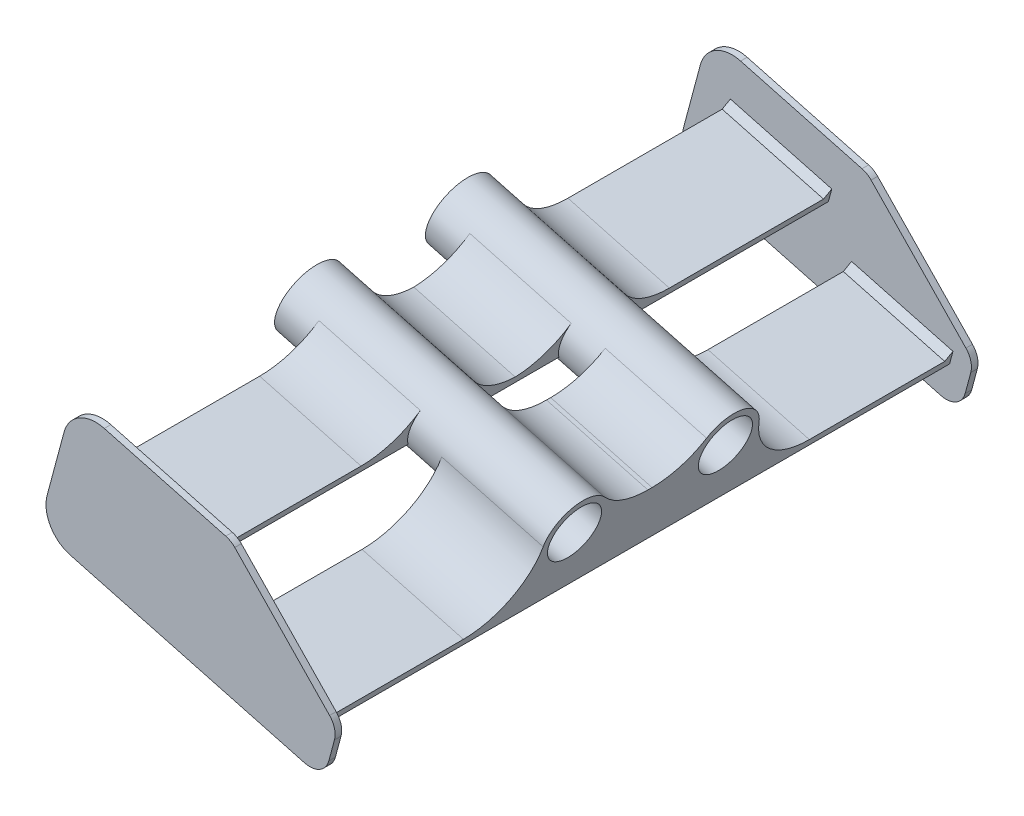
SolidWorks part; units mm, degrees
ref_plane "Front Plane" through (0, 0, 0) normal (0, 0, 1) x (1, 0, 0)
ref_plane "Top Plane" through (0, 0, 0) normal (0, 1, 0) x (1, 0, 0)
ref_plane "Right Plane" through (0, 0, 0) normal (1, 0, 0) x (0, 0, -1)
sketch "Sketch1" plane through (0, 0, 0) normal (0, 0, 1) x (1, 0, 0)
  line L0 (-1.1807, 1.2211) -> (-15.6351, 16.1701)
  line L1 (-17.0153, 16.9826) -> (-35.5312, 21.9439)
  line L2 (-41.6549, 18.4083) -> (-44.2431, 8.7491)
  line L3 (-40.7076, 2.6254) -> (-4.9683, -6.9509)
  line L4 (-1.2941, -4.8296) -> (-0.4396, -1.6407)
  line L5 (31.2953, -7.7274) -> (-61.4407, -7.7274) construction
  arc A0 (-4.9683, -6.9509) -> (-1.2941, -4.8296) centre (-4.1919, -4.0532) ccw
  arc A1 (-1.1807, 1.2211) -> (-0.4396, -1.6407) centre (-3.3374, -0.8642) cw
  arc A2 (-15.6351, 16.1701) -> (-17.0153, 16.9826) centre (-17.7918, 14.0848) ccw
  arc A3 (-44.2431, 8.7491) -> (-40.7076, 2.6254) centre (-39.4135, 7.455) ccw
  arc A4 (-35.5312, 21.9439) -> (-41.6549, 18.4083) centre (-36.8253, 17.1142) ccw
  point P10 (-2.0706, -7.7274)
  point P13 (0, 0)
  point P16 (-16.2127, 16.7675)
  point P19 (-45.5372, 3.9195)
  point P22 (-40.3608, 23.238)
  dimension "D6" = 3
  dimension "D7" = 5
  dimension "D1" = 15
  dimension "D2" = 45
  dimension "D3" = 20
  dimension "D4" = 25
  dimension "D5" = 8
extrude "Boss-Extrude1" add sketch "Sketch1" against normal blind 1
sketch "Sketch2" plane through (0, 0, -1) normal (0, 0, -1) x (-1, 0, 0)
  line L0 (3.4154, -1.1554) -> (3.6742, -2.1213)
  line L1 (3.6742, -2.1213) -> (19.129, 2.0198)
  line L2 (19.129, 2.0198) -> (18.8702, 2.9857)
  line L3 (18.8702, 2.9857) -> (3.4154, -1.1554)
  line L4 (21.8881, 11.0413) -> (22.1469, 10.0754)
  line L5 (22.1469, 10.0754) -> (37.6018, 14.2165)
  line L6 (37.6018, 14.2165) -> (37.3429, 15.1824)
  line L7 (37.3429, 15.1824) -> (21.8881, 11.0413)
  line L8 (40.7076, 2.6254) -> (4.9683, -6.9509) construction
  line L9 (1.2941, -4.8296) -> (0.4396, -1.6407) construction
  line L10 (41.6549, 18.4083) -> (44.2431, 8.7491) construction
  dimension "D1" = 3
  dimension "D2" = 16
  dimension "D3" = 16
  dimension "D4" = 1
  dimension "D5" = 1
  dimension "D6" = 5
  dimension "D7" = 5
  dimension "D8" = 12
extrude "Boss-Extrude2" add sketch "Sketch2" along normal blind 96
sketch "Sketch3" plane through (0, 0, -97) normal (0, 0, -1) x (-1, 0, 0)
  line L5 (4.9683, -6.9509) -> (40.7076, 2.6254)
  line L6 (44.2431, 8.7491) -> (41.6549, 18.4083)
  line L7 (35.5312, 21.9439) -> (17.0153, 16.9826)
  line L8 (15.6351, 16.1701) -> (1.1807, 1.2211)
  line L9 (0.4396, -1.6407) -> (1.2941, -4.8296)
  line L10 (4.9683, -6.9509) -> (40.7076, 2.6254)
  line L11 (44.2431, 8.7491) -> (41.6549, 18.4083)
  line L12 (35.5312, 21.9439) -> (17.0153, 16.9826)
  line L13 (15.6351, 16.1701) -> (1.1807, 1.2211)
  line L14 (0.4396, -1.6407) -> (1.2941, -4.8296)
  arc A5 (1.2941, -4.8296) -> (4.9683, -6.9509) centre (4.1919, -4.0532) ccw
  arc A6 (40.7076, 2.6254) -> (44.2431, 8.7491) centre (39.4135, 7.455) ccw
  arc A7 (41.6549, 18.4083) -> (35.5312, 21.9439) centre (36.8253, 17.1142) ccw
  arc A8 (17.0153, 16.9826) -> (15.6351, 16.1701) centre (17.7918, 14.0848) ccw
  arc A9 (1.1807, 1.2211) -> (0.4396, -1.6407) centre (3.3374, -0.8642) ccw
  arc A10 (1.2941, -4.8296) -> (4.9683, -6.9509) centre (4.1919, -4.0532) ccw
  arc A11 (40.7076, 2.6254) -> (44.2431, 8.7491) centre (39.4135, 7.455) ccw
  arc A12 (41.6549, 18.4083) -> (35.5312, 21.9439) centre (36.8253, 17.1142) ccw
  arc A13 (17.0153, 16.9826) -> (15.6351, 16.1701) centre (17.7918, 14.0848) ccw
  arc A14 (1.1807, 1.2211) -> (0.4396, -1.6407) centre (3.3374, -0.8642) ccw
  dimension "D1" = 0
extrude "Boss-Extrude3" add sketch "Sketch3" along normal blind 1
ref_plane "Symmetry-Plane1" through (0, 0, -49) normal (0, 0, 1) x (1, 0, 0)
sketch "Sketch4" plane through (-2.8978, 0.7765, 0) normal (0.9659, -0.2588, 0) x (0, 0, -1)
  line L0 (32.5, -3) -> (32.5, 6)
  line L1 (97, -3) -> (1, -3) construction
  line L2 (55.5, 6) -> (42.5, 6)
  line L3 (49, 16.0421) -> (49, -16.0421) construction
  line L4 (49, 6) -> (49, -3)
  line L5 (65.5, -3) -> (32.5, -3)
  line L6 (65.5, -3) -> (65.5, 6)
  line L7 (97, -2) -> (1, -2) construction
  arc A0 (49, -3.083) -> (49.129, -3) centre (43.25, 6) ccw
  arc A1 (32.5, 6) -> (42.5, 6) centre (37.5, 6) ccw
  arc A2 (49, -3.083) -> (48.871, -3) centre (54.75, 6) cw
  arc A3 (65.5, 6) -> (55.5, 6) centre (60.5, 6) cw
  line M8 (97, -2) -> (1, -2)
  dimension "D1" = 8
  dimension "D2" = 33
extrude "Boss-Extrude4" add sketch "Sketch4" against normal up to surface (16 mm away) contours L6 A3 L2 L4 M8 | A1 L0 L4 L2 M8 up to face at (-18.9996, 2.5027, -49)
sketch "Sketch5" plane through (-2.8978, 0.7765, 0) normal (0.9659, -0.2588, 0) x (0, 0, -1)
  arc A0 (55.5, 6) -> (65.5, 6) centre (60.5, 6) ccw construction
  arc A1 (55.5, 6) -> (65.5, 6) centre (60.5, 6) ccw
  arc A2 (32.5, 6) -> (42.5, 6) centre (37.5, 6) ccw construction
  arc A3 (32.5, 6) -> (42.5, 6) centre (37.5, 6) ccw
  arc A4 (65.5, 6) -> (55.5, 6) centre (60.5, 6) ccw
  arc A5 (42.5, 6) -> (32.5, 6) centre (37.5, 6) ccw
  arc M6 (65.5, 6) -> (55.5, 6) centre (60.5, 6) cw
  arc M8 (42.5, 6) -> (32.5, 6) centre (37.5, 6) cw
extrude "Extrude-Thin1" add sketch "Sketch5" against normal up to surface (42 mm away) thin contours A4 M6 | A5 M8 up to face at (-42.949, 13.5787, -97.5) thin type one direction reverse wall 1
sketch "Sketch6" plane through (-23.1822, 6.2117, 0) normal (0.9659, -0.2588, 0) x (0, 0, -1)
  line L2 (57.0359, 4) -> (63.9641, 4)
  line L3 (64.373, 5) -> (56.627, 5)
  line L4 (57.0359, 4) -> (63.9641, 4)
  line L5 (64.373, 5) -> (56.627, 5)
  arc A2 (63.9641, 4) -> (64.373, 5) centre (60.5, 6) ccw
  arc A3 (56.627, 5) -> (57.0359, 4) centre (60.5, 6) ccw
  arc A4 (63.9641, 4) -> (64.373, 5) centre (60.5, 6) ccw
  arc A5 (56.627, 5) -> (57.0359, 4) centre (60.5, 6) ccw
  dimension "D1" = 0
extrude "Cut-Extrude1" cut sketch "Sketch6" against normal through all
sketch "Sketch7" plane through (-23.1822, 6.2117, 0) normal (0.9659, -0.2588, 0) x (0, 0, -1)
  line L2 (34.0359, 4) -> (40.9641, 4)
  line L3 (41.373, 5) -> (33.627, 5)
  line L4 (34.0359, 4) -> (40.9641, 4)
  line L5 (41.373, 5) -> (33.627, 5)
  arc A2 (40.9641, 4) -> (41.373, 5) centre (37.5, 6) ccw
  arc A3 (33.627, 5) -> (34.0359, 4) centre (37.5, 6) ccw
  arc A4 (40.9641, 4) -> (41.373, 5) centre (37.5, 6) ccw
  arc A5 (33.627, 5) -> (34.0359, 4) centre (37.5, 6) ccw
  dimension "D1" = 0
extrude "Cut-Extrude2" cut sketch "Sketch7" against normal through all
fillet "Fillet1" radius 10 2 edges at (-11.1428, 0.9152, -65.5) (-11.1428, 0.9152, -32.5)
fillet "Fillet2" radius 10 2 edges at (-29.6155, 13.1118, -65.399) (-29.6155, 13.1118, -32.601)
fillet "Fillet3" radius 10 2 edges at (-29.6155, 13.1118, -55.601) (-29.6155, 13.1118, -42.399)
fillet "Fillet4" radius 10 2 edges at (-9.0723, 8.6426, -55.5) (-9.0723, 8.6426, -42.5)
chamfer "Chamfer1" distance 1 angle 45 2 edges at (-11.1428, 0.9152, -1) (-11.1428, 0.9152, -97)
chamfer "Chamfer2" distance 1 angle 45 2 edges at (-29.6155, 13.1118, -97) (-29.6155, 13.1118, -1)
sketch "Sketch8" plane through (-0.7765, -2.8978, 0) normal (-0.2588, -0.9659, 0) x (0.9659, -0.2588, 0)
  line L0 (-3, -1) -> (-19, -1) construction
  line L1 (-3, -97) -> (-19, -97) construction
  line L2 (-11, -97) -> (-11, -1) construction
  circle A0 centre (-11, -49) radius 1
extrude "Cut-Extrude3" cut sketch "Sketch8" against normal blind 3
